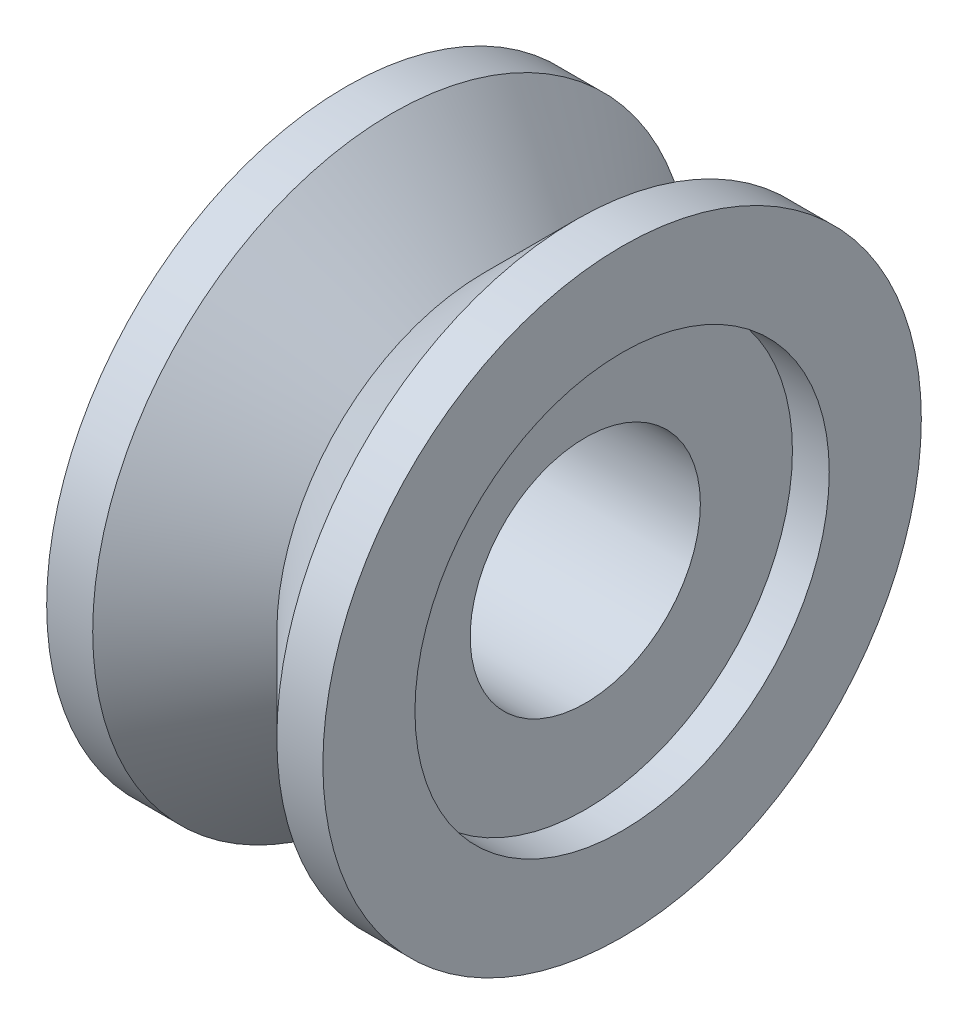
SolidWorks part; units mm, degrees
ref_plane "Front Plane" through (0, 0, 0) normal (0, 0, 1) x (1, 0, 0)
ref_plane "Top Plane" through (0, 0, 0) normal (0, 1, 0) x (1, 0, 0)
ref_plane "Right Plane" through (0, 0, 0) normal (1, 0, 0) x (0, 0, -1)
sketch "Sketch1" plane through (0, 0, 0) normal (1, 0, 0) x (0, 0, -1)
  circle A0 centre (0, 0) radius 6.5
  dimension "D1" = 13
extrude "Boss-Extrude1" add sketch "Sketch1" along normal mid plane 6
sketch "Sketch2" plane through (0, 0, 0) normal (0, 0, 1) x (1, 0, 0)
  line L0 (-2, 6.5) -> (0, 4.5)
  line L1 (0, 4.5) -> (2, 6.5)
  line L2 (3, 6.5) -> (-3, 6.5) construction
  line L3 (2, 6.5) -> (-2, 6.5)
  line L4 (0, 4.5) -> (0, 0) construction
  line L6 (0, 4.5) -> (0, 6.5) construction
  dimension "D1" = 4
  dimension "Width" = 90
revolve "Cut-Revolve1" cut sketch "Sketch2" angle 360 about axis through (3, 0, 0) along (-1, 0, 0)
sketch "Sketch4" plane through (3, 0, 0) normal (1, 0, 0) x (0, 0, -1)
  circle A0 centre (0, 0) radius 4.5
  dimension "D1" = 9
extrude "Cut-Extrude1" cut sketch "Sketch4" against normal blind 0.8
mirror "Mirror1" about plane through (0, 0, 0) normal (1, 0, 0) of "Cut-Extrude1"
sketch "Sketch5" plane through (0, 0, 0) normal (1, 0, 0) x (0, 0, -1)
  circle A0 centre (0, 0) radius 2.5
  dimension "D1" = 5
extrude "Cut-Extrude2" cut sketch "Sketch5" against normal through all both and the other way through all
ref_axis "Axis1" through (-2.2, 0, 0) along (1, 0, 0)
sketch "Sketch6" plane through (0, 0, 0) normal (0, 1, 0) x (1, 0, 0)
  line L0 (0, 4.5) -> (-2, 6.5) construction
  line L1 (2, 6.5) -> (0, 4.5) construction
  circle A0 centre (0, 6.6213) radius 1.5
  dimension "D1" = 3
